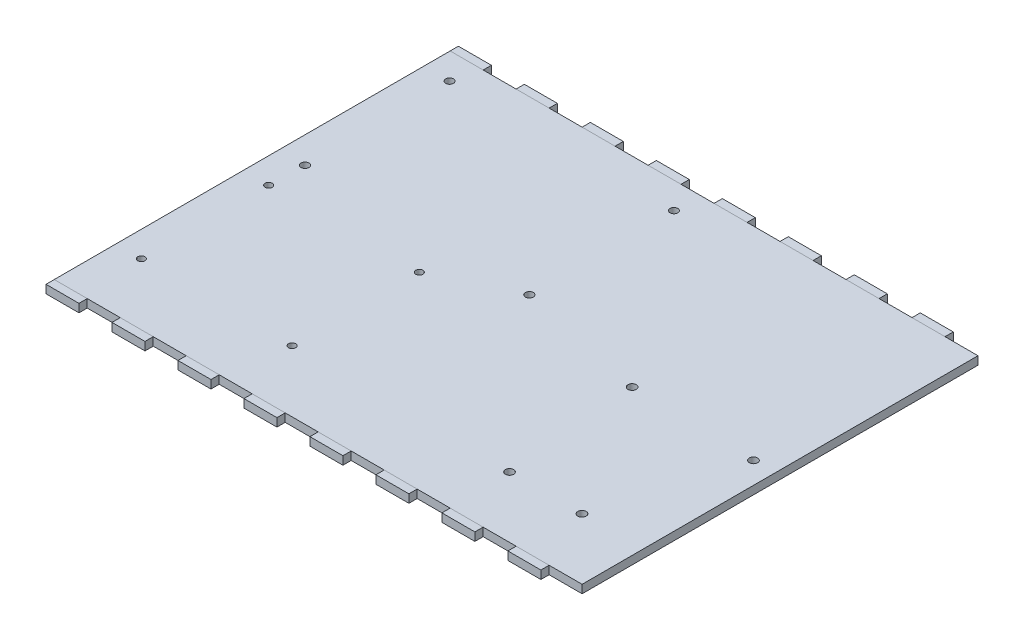
SolidWorks part; units mm, degrees
ref_plane "Front" through (0, 0, 0) normal (0, 0, 1) x (1, 0, 0)
ref_plane "Top" through (0, 0, 0) normal (0, 1, 0) x (1, 0, 0)
ref_plane "Right" through (0, 0, 0) normal (1, 0, 0) x (0, 0, -1)
sketch "Sketch1" plane through (0, 0, 0) normal (0, 1, 0) x (1, 0, 0)
  line L1 (0, 0) -> (203.2, 0)
  line L2 (0, 0) -> (0, 152.4)
  line L3 (0, 152.4) -> (203.2, 152.4)
  line L4 (203.2, 0) -> (203.2, 152.4)
  dimension "D1" = 203.2
  dimension "D2" = 152.4
extrude "Boss-Extrude1" add sketch "Sketch1" along normal blind 3.175
sketch "Sketch2" plane through (0, 3.175, 0) normal (0, 1, 0) x (1, 0, 0)
  line L0 (25.4, 0) -> (25.4, -3.175)
  line L1 (0, 0) -> (12.7, 0)
  line L2 (0, 0) -> (0, -3.175)
  line L3 (0, -3.175) -> (12.7, -3.175)
  line L4 (12.7, 0) -> (12.7, -3.175)
  line L5 (25.4, 0) -> (38.1, 0)
  line L6 (38.1, 0) -> (38.1, -3.175)
  line L7 (25.4, -3.175) -> (38.1, -3.175)
  line L8 (50.8, 0) -> (50.8, -3.175)
  line L9 (50.8, 0) -> (63.5, 0)
  line L10 (63.5, 0) -> (63.5, -3.175)
  line L11 (50.8, -3.175) -> (63.5, -3.175)
  line L12 (76.2, 0) -> (76.2, -3.175)
  line L13 (76.2, 0) -> (88.9, 0)
  line L14 (88.9, 0) -> (88.9, -3.175)
  line L15 (76.2, -3.175) -> (88.9, -3.175)
  line L16 (101.6, 0) -> (101.6, -3.175)
  line L17 (101.6, 0) -> (114.3, 0)
  line L18 (114.3, 0) -> (114.3, -3.175)
  line L19 (101.6, -3.175) -> (114.3, -3.175)
  line L20 (127, 0) -> (127, -3.175)
  line L21 (127, 0) -> (139.7, 0)
  line L22 (139.7, 0) -> (139.7, -3.175)
  line L23 (127, -3.175) -> (139.7, -3.175)
  line L24 (152.4, 0) -> (152.4, -3.175)
  line L25 (152.4, 0) -> (165.1, 0)
  line L26 (165.1, 0) -> (165.1, -3.175)
  line L27 (152.4, -3.175) -> (165.1, -3.175)
  line L28 (177.8, 0) -> (177.8, -3.175)
  line L29 (177.8, 0) -> (190.5, 0)
  line L30 (190.5, 0) -> (190.5, -3.175)
  line L31 (177.8, -3.175) -> (190.5, -3.175)
  line L32 (0, 76.2) -> (203.2, 76.2) construction
  line L33 (0, 152.4) -> (0, 0) construction
  line L34 (203.2, 0) -> (203.2, 152.4) construction
  line L35 (177.8, 152.4) -> (190.5, 152.4)
  line L36 (190.5, 152.4) -> (190.5, 155.575)
  line L37 (177.8, 155.575) -> (190.5, 155.575)
  line L38 (177.8, 152.4) -> (177.8, 155.575)
  line L39 (152.4, 152.4) -> (165.1, 152.4)
  line L40 (165.1, 152.4) -> (165.1, 155.575)
  line L41 (152.4, 155.575) -> (165.1, 155.575)
  line L42 (152.4, 152.4) -> (152.4, 155.575)
  line L43 (127, 152.4) -> (139.7, 152.4)
  line L44 (139.7, 152.4) -> (139.7, 155.575)
  line L45 (127, 155.575) -> (139.7, 155.575)
  line L46 (127, 152.4) -> (127, 155.575)
  line L47 (101.6, 152.4) -> (114.3, 152.4)
  line L48 (114.3, 152.4) -> (114.3, 155.575)
  line L49 (101.6, 155.575) -> (114.3, 155.575)
  line L50 (101.6, 152.4) -> (101.6, 155.575)
  line L51 (76.2, 152.4) -> (88.9, 152.4)
  line L52 (88.9, 152.4) -> (88.9, 155.575)
  line L53 (76.2, 155.575) -> (88.9, 155.575)
  line L54 (76.2, 152.4) -> (76.2, 155.575)
  line L55 (50.8, 152.4) -> (63.5, 152.4)
  line L56 (63.5, 152.4) -> (63.5, 155.575)
  line L57 (50.8, 155.575) -> (63.5, 155.575)
  line L58 (50.8, 152.4) -> (50.8, 155.575)
  line L59 (25.4, 152.4) -> (38.1, 152.4)
  line L60 (38.1, 152.4) -> (38.1, 155.575)
  line L61 (25.4, 155.575) -> (38.1, 155.575)
  line L62 (25.4, 152.4) -> (25.4, 155.575)
  line L63 (0, 155.575) -> (12.7, 155.575)
  line L64 (12.7, 152.4) -> (12.7, 155.575)
  line L65 (0, 152.4) -> (12.7, 152.4)
  line L66 (0, 152.4) -> (0, 155.575)
  dimension "D1" = 3.175
  dimension "D2" = 12.7
  dimension "D3" = 8
extrude "Boss-Extrude2" add sketch "Sketch2" against normal blind 3.175 separate body
sketch "Sketch4" plane through (-65.6185, 3.175, -114.5289) normal (0, 1, 0) x (1, 0, 0)
  line L0 (104.4685, -38.3289) -> (104.4685, -94.3289) construction
  line L1 (74.9685, -94.3289) -> (153.9685, -94.3289) construction
  line L2 (71.9685, -91.3289) -> (71.9685, -41.3289) construction
  line L3 (74.9685, -38.3289) -> (153.9685, -38.3289) construction
  line L4 (156.9685, -91.3289) -> (156.9685, -41.3289) construction
  line L10 (65.6185, 37.8711) -> (65.6185, -114.5289) construction
  line L12 (268.8185, 37.8711) -> (65.6185, 37.8711) construction
  arc A0 (74.9685, -94.3289) -> (71.9685, -91.3289) centre (74.9685, -91.3289) cw construction
  arc A1 (153.9685, -94.3289) -> (156.9685, -91.3289) centre (153.9685, -91.3289) ccw construction
  arc A2 (153.9685, -38.3289) -> (156.9685, -41.3289) centre (153.9685, -41.3289) cw construction
  arc A3 (71.9685, -41.3289) -> (74.9685, -38.3289) centre (74.9685, -41.3289) cw construction
  circle A4 centre (75.4685, -41.8289) radius 1.375
  circle A5 centre (75.4685, -90.8289) radius 1.375
  circle A6 centre (133.4685, -90.8289) radius 1.375
  circle A7 centre (133.4685, -41.8289) radius 1.375
  point P7 (71.9685, -94.3289)
  point P12 (156.9685, -38.3289)
  point P15 (71.9685, -38.3289)
  dimension "D3" = 3
  dimension "D4" = 2.75
  dimension "D1" = 56
  dimension "D2" = 85
  dimension "D5" = 49
  dimension "D6" = 3.5
  dimension "D7" = 3.5
  dimension "D8" = 58
  dimension "D9" = 6.35
  dimension "D10" = 76.2
extrude "Cut-Extrude1" cut sketch "Sketch4" against normal through all
sketch "Sketch5" plane through (-58.3327, 3.175, -175.8659) normal (0, 1, 0) x (0, 0, 1)
  line L0 (86.4754, 202.6489) -> (86.4754, 255.9489) construction
  line L1 (86.4754, 255.9489) -> (150.2443, 255.9489) construction
  line L2 (150.2443, 255.9489) -> (152.3754, 253.8178) construction
  line L3 (155.2754, 240.1078) -> (155.2754, 208.2989) construction
  line L4 (155.2754, 208.2989) -> (152.3754, 205.3989) construction
  line L5 (152.3754, 205.3989) -> (152.3754, 202.6489) construction
  line L6 (152.3754, 202.6489) -> (86.4754, 202.6489) construction
  line L7 (152.3754, 253.8178) -> (152.3754, 243.0078) construction
  line L8 (152.3754, 243.0078) -> (155.2754, 240.1078) construction
  circle A0 centre (100.4754, 205.3989) radius 1.6
  circle A1 centre (101.5754, 253.1989) radius 1.6
  circle A2 centre (152.3754, 210.0989) radius 1.6
  circle A3 centre (152.3754, 237.9989) radius 1.6
  dimension "D3" = 3.2
  dimension "D12" = 50.8
  dimension "D7" = 51.9
  dimension "D1" = 53.3
  dimension "D2" = 68.8
  dimension "D4" = 15.2
  dimension "D5" = 14
  dimension "D6" = 2.75
  dimension "D8" = 51.9
  dimension "D9" = 1.1
  dimension "D10" = 4.7
  dimension "D11" = 2.75
  dimension "D13" = 45
  dimension "D14" = 45
  dimension "D16" = 45
extrude "Cut-Extrude2" cut sketch "Sketch5" against normal through all
sketch "Sketch10" plane through (154.7382, 3.175, -89.7842) normal (0, 1, 0) x (0, 0, -1)
  line L0 (-4.9142, 54.3882) -> (53.9458, 54.3882) construction
  line L1 (-7.2342, 56.7082) -> (-7.2342, 146.0682) construction
  line L2 (-4.9142, 148.3882) -> (53.9458, 148.3882) construction
  line L3 (56.2658, 56.7082) -> (56.2658, 146.0682) construction
  line L4 (-7.2342, 54.3882) -> (56.2658, 148.3882) construction
  line L5 (-7.2342, 148.3882) -> (56.2658, 54.3882) construction
  line L6 (62.6158, 154.7382) -> (-89.7842, 154.7382) construction
  line L7 (62.6158, -48.4618) -> (62.6158, 154.7382) construction
  line L8 (-3.4238, 144.5682) -> (-3.4238, 58.2082) construction
  arc A0 (-4.9142, 54.3882) -> (-7.2342, 56.7082) centre (-4.9142, 56.7082) cw construction
  arc A1 (53.9458, 54.3882) -> (56.2658, 56.7082) centre (53.9458, 56.7082) ccw construction
  arc A2 (53.9458, 148.3882) -> (56.2658, 146.0682) centre (53.9458, 146.0682) cw construction
  arc A3 (-4.9142, 148.3882) -> (-7.2342, 146.0682) centre (-4.9142, 146.0682) ccw construction
  circle A4 centre (-66.0842, 86.8882) radius 1.375 construction
  circle A5 centre (-3.4238, 144.5682) radius 1.535
  circle A6 centre (52.4558, 144.7859) radius 1.5
  circle A7 centre (-3.4238, 58.2082) radius 1.535
  circle A8 centre (52.4558, 58.4259) radius 1.5
  point P0 (24.5158, 101.3882)
  dimension "D3" = 2.32
  dimension "D6" = 3.07
  dimension "D7" = 3
  dimension "D1" = 63.5
  dimension "D2" = 94
  dimension "D4" = 6.35
  dimension "D5" = 6.35
  dimension "D8" = 55.88
  dimension "D9" = 27.94
  dimension "D10" = 43.18
  dimension "D12" = 86.36
  dimension "D11" = 2
extrude "Cut-Extrude3" cut sketch "Sketch10" against normal through all both and the other way through all
